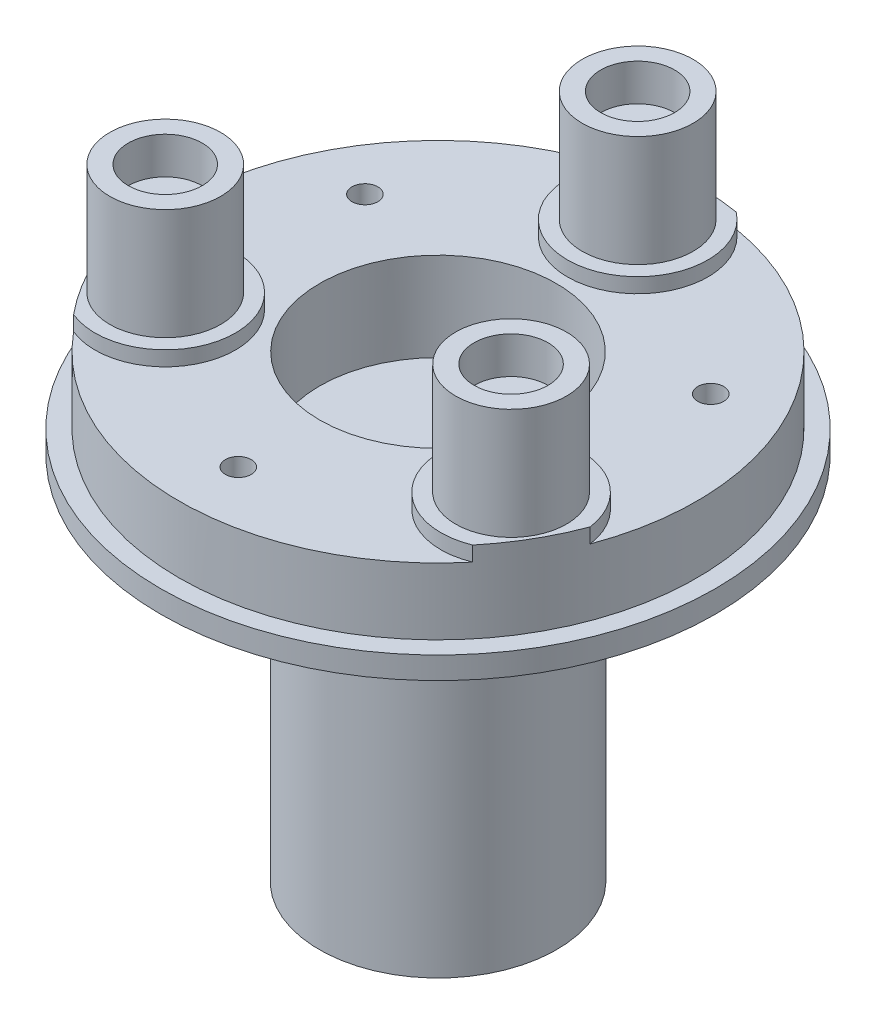
SolidWorks part; units mm, degrees
note: The reader was unsure of these and kept them because the rebuilt part matched: shared geometry of "Sketch1<3>".
ref_plane "Front Plane" through (0, 0, 0) normal (0, 0, 1) x (1, 0, 0)
ref_plane "Top Plane" through (0, 0, 0) normal (0, 1, 0) x (1, 0, 0)
ref_plane "Right Plane" through (0, 0, 0) normal (1, 0, 0) x (0, 0, -1)
sketch "Sketch1" plane through (0, 0, 0) normal (0, 1, 0) x (1, 0, 0)
  line L0 (0, 0) -> (0, 44.6523) construction
  circle A4 centre (0, 0) radius 37.5
  circle A5 centre (0, 0) radius 35
  arc A6 (-10.4425, 33.4059) -> (10.4425, 33.4059) centre (0, 30) ccw
  circle A7 centre (0, 0) radius 35
  arc A8 (34.1516, -7.6594) -> (23.7091, -25.7465) centre (25.9808, -15) ccw
  arc A9 (-23.7091, -25.7465) -> (-34.1516, -7.6594) centre (-25.9808, -15) ccw
  point P17 (0, 0)
  dimension "D1" = 75
  dimension "D2" = 70
  dimension "D3" = 30
  dimension "D4" = 3
extrude "Boss-Extrude1" add sketch "Sketch1" along normal blind 3 contours A4
extrude "Boss-Extrude2" add sketch "Sketch1<3>" along normal blind 12
sketch "Sketch1<3>" plane through (0, 0, 0) normal (0, 1, 0) x (1, 0, 0) same geometry as "Sketch1"
sketch "Sketch13" plane through (0, 12, 0) normal (0, 1, 0) x (1, 0, 0)
  circle A0 centre (0, 0) radius 16
  dimension "D1" = 32
extrude "Cut-Extrude6" cut sketch "Sketch13" against normal through all
sketch "Sketch24" plane through (0, 12, 0) normal (0, 1, 0) x (1, 0, 0)
  line L0 (0, 0) -> (0, 27.027) construction
  arc A0 (-5.813, 34.5139) -> (5.813, 34.5139) centre (0, 27) ccw
  circle A1 centre (0, 0) radius 35
  arc A2 (32.7964, -12.2227) -> (26.9834, -22.2912) centre (23.3827, -13.5) ccw
  arc A3 (-26.9834, -22.2912) -> (-32.7964, -12.2227) centre (-23.3827, -13.5) ccw
  point P15 (0, 0)
  dimension "D1" = 19
  dimension "D4" = 70
  dimension "D2" = 27
  dimension "D3" = 3
extrude "Boss-Extrude9" add sketch "Sketch24" along normal blind 2
sketch "Sketch25" plane through (0, 14, 0) normal (0, 1, 0) x (1, 0, 0)
  line L0 (0, 0) -> (0, 55.8426) construction
  circle A0 centre (0, 27) radius 7.5
  circle A1 centre (23.3827, -13.5) radius 7.5
  circle A2 centre (-23.3827, -13.5) radius 7.5
  point P11 (0, 0)
  dimension "D2" = 15
  dimension "D1" = 27
  dimension "D3" = 3
extrude "Boss-Extrude10" add sketch "Sketch25" along normal blind 15
sketch "Sketch26" plane through (0, 29, 0) normal (0, 1, 0) x (1, 0, 0)
  line L0 (0, 0) -> (0, 38.3857) construction
  circle A0 centre (0, 27) radius 5
  circle A1 centre (23.3827, -13.5) radius 5
  circle A2 centre (-23.3827, -13.5) radius 5
  point P11 (0, 0)
  dimension "D2" = 10
  dimension "D1" = 27
  dimension "D3" = 3
extrude "Cut-Extrude9" cut sketch "Sketch26" against normal blind 5
hole_wizard "CBORE for M3 Pan Head Machine Screw1" positions "Sketch27" profile "Sketch28" counterbore size "M3" standard "ANSI Metric" end condition through all
sketch "Sketch27" plane through (0, 0, 0) normal (0, -1, 0) x (-1, 0, 0)
  point P0 (0, 27)
  point P9 (23.3827, -13.5)
  point P10 (-23.3827, -13.5)
  dimension "D1" = 27
  dimension "D2" = 3
sketch "Sketch28" plane through (0, 0, -27) normal (1, 0, 0) x (0, 0, -1)
  line L0 (0, 0) -> (0, 29)
  line L1 (0, 29) -> (1.8, 29)
  line L3 (1.8, 29) -> (1.8, 2.4)
  line L4 (3.5, 2.4) -> (1.8, 2.4)
  line L5 (3.5, 2.4) -> (3.5, 0.025)
  line L6 (3.5, 0.025) -> (3.525, 0)
  line L7 (3.525, 0) -> (0, 0)
  line L8 (-3.5, 0.025) -> (-3.525, 0) construction
  line L11 (0, -6.35) -> (0, 107.95) construction
  dimension "Thru Hole Dia." = 3.6
  dimension "Thru Hole Depth" = 29
  dimension "C'Bore Dia." = 7
  dimension "C'Bore Depth" = 2.4
  dimension "Near C'Sink Dia." = 7.05
  dimension "Near C'Sink Angle" = 90
sketch "Sketch29" plane through (0, 12, 0) normal (0, 1, 0) x (1, 0, 0)
  line L0 (0, 0) -> (23.3827, 13.5) construction
  line L1 (0, 0) -> (0, 14.4601) construction
  circle A0 centre (23.3827, 13.5) radius 1.75
  circle A1 centre (0, -27) radius 1.75
  circle A2 centre (-23.3827, 13.5) radius 1.75
  point P11 (0, 0)
  dimension "D3" = 3.5
  dimension "D1" = 60
  dimension "D2" = 27
  dimension "D4" = 3
extrude "Cut-Extrude10" cut sketch "Sketch29" against normal through all
sketch "Sketch30" plane through (0, 12, 0) normal (0, -1, 0) x (1, 0, 0)
  circle A0 centre (0, 0) radius 16
sketch "Sketch31" plane through (0, 0, 0) normal (0, -1, 0) x (1, 0, 0)
  circle A0 centre (0, 0) radius 16.05
extrude "Boss-Extrude11" add sketch "Sketch31" along normal blind 50 separate body
sketch "Sketch32" plane through (0, 0, 0) normal (0, -1, 0) x (1, 0, 0)
  circle A0 centre (0, 0) radius 16
  circle A1 centre (0, 0) radius 18
  dimension "D1" = 36
extrude "Boss-Extrude12" add sketch "Sketch32" along normal blind 1.11
